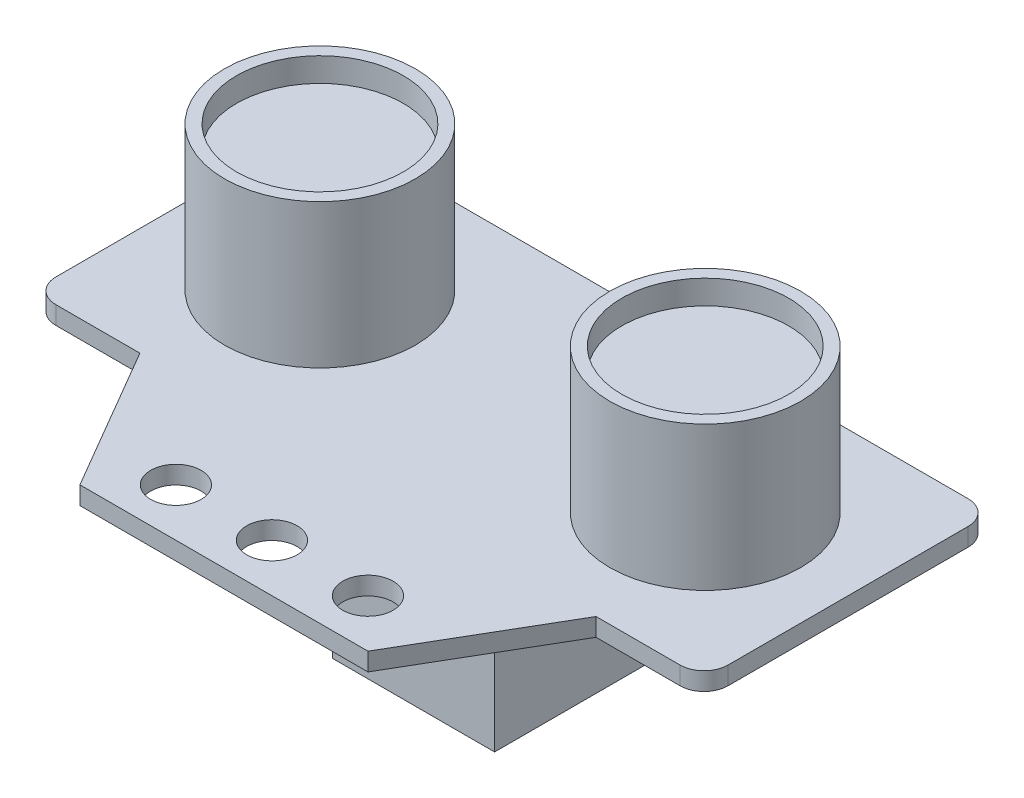
SolidWorks part; units mm, degrees
ref_plane "Front Plane" through (0, 0, 0) normal (0, 0, 1) x (1, 0, 0)
ref_plane "Top Plane" through (0, 0, 0) normal (0, 1, 0) x (1, 0, 0)
ref_plane "Right Plane" through (0, 0, 0) normal (1, 0, 0) x (0, 0, -1)
sketch "Sketch1" plane through (0, 0, 0) normal (0, 1, 0) x (1, 0, 0)
  line L0 (12, 0) -> (-12, 0)
  line L1 (-12, 0) -> (-19, 12)
  line L2 (-19, 12) -> (-28, 12)
  line L3 (-28, 12) -> (-28, 36)
  line L4 (-28, 36) -> (28, 36)
  line L5 (0, 36) -> (0, 0) construction
  line L6 (28, 12) -> (28, 36)
  line L7 (19, 12) -> (28, 12)
  line L8 (12, 0) -> (19, 12)
  line L9 (-8, 4) -> (8, 4) construction
  circle A0 centre (0, 4) radius 2.1
  circle A1 centre (-8, 4) radius 2.1
  circle A2 centre (8, 4) radius 2.1
  dimension "D6" = 4.2
  dimension "D1" = 56
  dimension "D2" = 36
  dimension "D3" = 24
  dimension "D4" = 24
  dimension "D5" = 9
  dimension "D7" = 1.9
  dimension "D8" = 16
extrude "Boss-Extrude1" add sketch "Sketch1" along normal blind 1.5
fillet "Fillet1" radius 2 4 edges at (28, 0.75, -12) (28, 0.75, -36) (-28, 0.75, -36) (-28, 0.75, -12)
sketch "Sketch2" plane through (0, 1.5, 0) normal (0, 1, 0) x (1, 0, 0)
  line L0 (0, 0) -> (0, 36) construction
  line L1 (26, 36) -> (-26, 36) construction
  line L2 (-28, 34) -> (-28, 14) construction
  circle A0 centre (-16.05, 24.05) radius 7.95
  circle A1 centre (16.05, 24.05) radius 7.95
  dimension "D1" = 15.9
  dimension "D2" = 4
  dimension "D3" = 4
extrude "Boss-Extrude2" add sketch "Sketch2" along normal blind 12
sketch "Sketch3" plane through (0, 0, 0) normal (0, -1, 0) x (1, 0, 0)
  line L0 (26, -36) -> (-26, -36) construction
  line L1 (-6.75, -15.8) -> (6.75, -15.8)
  line L2 (-6.75, -15.8) -> (-6.75, -31.8)
  line L3 (-6.75, -31.8) -> (6.75, -31.8)
  line L4 (6.75, -15.8) -> (6.75, -31.8)
  point P4 (0, -15.8)
  dimension "D1" = 13.5
  dimension "D2" = 16
  dimension "D3" = 4.2
extrude "Boss-Extrude3" add sketch "Sketch3" along normal blind 16.3
sketch "Sketch4" plane through (0, 13.5, 0) normal (0, 1, 0) x (1, 0, 0)
  circle A3 centre (-16.05, 24.05) radius 6.95
  circle A4 centre (-16.05, 24.05) radius 6.95
  circle A6 centre (16.05, 24.05) radius 6.95
  circle A7 centre (16.05, 24.05) radius 6.95
  dimension "D1" = 1
  dimension "D2" = 1
extrude "Cut-Extrude1" cut sketch "Sketch4" against normal blind 2
equation "\"width\"= 24"
equation "\"thk\"= 3"
equation "\"holesize\"= 4.2"
equation "\"holedistance\"= ( 20 + 12 ) / 2"
equation "\"threaded_hole\"= 3.9"
equation "\"fillet_radius\"= 2"
equation "\"ground_clearance\"= 25"
equation "\"tire_thk\"= 4"
equation "\"innerwheel_diam\" = \"wheel_diam\"-2*\"tire_thk\""
equation "\"innerwheel_thk\"= 8"
equation "\"wheel_diam\"= 2*(\"width\"/2+\"ground_clearance\")"
equation "\"D6@Sketch1\"=\"holesize\""
equation "\"D8@Sketch1\"=\"holedistance\""
